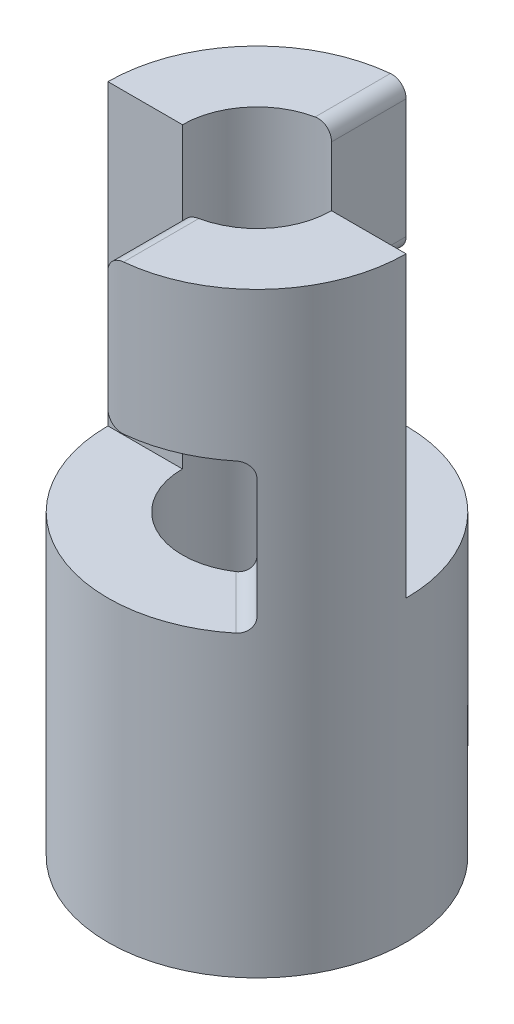
SolidWorks part; units mm, degrees
material "3D Printer ABS - Black"
ref_plane "Front Plane" through (0, 0, 0) normal (0, 0, 1) x (1, 0, 0)
ref_plane "Top Plane" through (0, 0, 0) normal (0, 1, 0) x (1, 0, 0)
ref_plane "Right Plane" through (0, 0, 0) normal (1, 0, 0) x (0, 0, -1)
sketch "Sketch1" plane through (0, 0, 0) normal (0, 1, 0) x (1, 0, 0)
  circle A0 centre (0, 0) radius 6.35
  circle A1 centre (0, 0) radius 3.175
  dimension "D1" = 12.7
extrude "Boss-Extrude1" add sketch "Sketch1" along normal blind 25.4
sketch "Sketch2" plane through (0, 25.4, 0) normal (0, 1, 0) x (1, 0, 0)
  line L0 (0, -3.175) -> (0, -6.35)
  line L1 (0, 3.175) -> (0, 6.35)
  line L2 (-6.35, 0) -> (-3.175, 0)
  line L3 (3.175, 0) -> (6.35, 0)
  circle A0 centre (0, 0) radius 6.35 construction
  circle A1 centre (0, 0) radius 3.175 construction
  circle A2 centre (0, 0) radius 6.35
  circle A3 centre (0, 0) radius 3.175
  circle M4 centre (0, 0) radius 6.35
  circle M5 centre (0, 0) radius 3.175
extrude "Cut-Extrude1" cut sketch "Sketch2" against normal blind 12.7 contours L2 L0 M4 M5 | L3 L1 M5 M4
sketch "Sketch3" plane through (0, 12.7, 0) normal (0, 1, 0) x (1, 0, 0)
  line L0 (4.4901, -4.4901) -> (2.2451, -2.2451)
  line L1 (-2.2451, 2.2451) -> (-4.4901, 4.4901)
  line L2 (0, 3.175) -> (0, 6.35) construction
  line L3 (0, 3.175) -> (0, 6.35)
  line L4 (3.175, 0) -> (6.35, 0) construction
  line L5 (3.175, 0) -> (6.35, 0) construction
  line L6 (0, -3.175) -> (0, -6.35) construction
  line L7 (0, -3.175) -> (0, -6.35)
  arc A0 (0, -6.35) -> (6.35, 0) centre (0, 0) ccw construction
  arc A1 (0, -3.175) -> (3.175, 0) centre (0, 0) ccw construction
  arc A2 (0, 3.175) -> (-3.175, 0) centre (0, 0) ccw construction
  arc A3 (0, 6.35) -> (-6.35, 0) centre (0, 0) ccw construction
  arc A4 (0, 6.35) -> (-4.4901, 4.4901) centre (0, 0) ccw
  arc A5 (0, 3.175) -> (-2.2451, 2.2451) centre (0, 0) ccw
  arc A6 (4.4901, -4.4901) -> (6.35, 0) centre (0, 0) ccw construction
  arc A7 (0, -6.35) -> (4.4901, -4.4901) centre (0, 0) ccw
  arc A8 (-2.2451, 2.2451) -> (-3.175, 0) centre (0, 0) ccw construction
  arc A9 (-4.4901, 4.4901) -> (-6.35, 0) centre (0, 0) ccw construction
  arc A10 (2.2451, -2.2451) -> (3.175, 0) centre (0, 0) ccw construction
  arc A11 (0, -3.175) -> (2.2451, -2.2451) centre (0, 0) ccw
  line M3 (0, -6.35) -> (0, -3.175)
extrude "Cut-Extrude2" [suppressed] cut sketch "Sketch3" along normal blind 6.35 contours A5 L3 A4 L1 | A11 A7 L0 M3
ref_plane "Wrap Plane" through (0, 0, 6.35) normal (0, 0, 1) x (1, 0, 0)
sketch "Sketch5" plane through (0, 0, 6.35) normal (0, 0, 1) x (1, 0, 0)
  line L3 (4.9873, 19.05) -> (0.635, 19.05)
  line L4 (4.9873, 19.05) -> (4.9873, 12.7)
  line L5 (4.9873, 12.7) -> (0, 12.7)
  line L6 (0, 12.7) -> (0, 19.05)
  line L7 (0, 19.05) -> (0, 19.685) construction
  line L8 (0, 12.7) -> (0, 25.4) construction
  line L9 (0.635, 19.05) -> (0, 19.05)
  arc A0 (0, 19.685) -> (0.635, 19.05) centre (0.635, 19.685) ccw construction
  dimension "D1" = 0.635
  dimension "D2" = 4.9873
  dimension "D3" = 6.35
wrap "Wrap6" sketch "Sketch5" wrap type deboss source sketch "Sketch5" thickness 3.175 face at (0, 0, 6.35) parameters "D1"=3.175
pattern_circular "CirPattern1" count 2 over 360 about axis through (0, 19.05, 0) along (0.7071, 0, 0.7071) of "Wrap6"
fillet "Fillet1" radius 0.635 10 edges at (0, 25.4, -4.7625) (0, 25.4, 4.7625) (3.3676, 12.7, 3.3676) (3.3676, 19.05, 3.3676) (0.4755, 19.05, 4.7387) (0, 19.05, 4.7625) (-3.3676, 12.7, -3.3676) (-3.3676, 19.05, -3.3676) (-0.4755, 19.05, -4.7387) (0, 19.05, -4.7625)
split "Split1" bodies to split 106 resulting bodies 107 108
equation "\"D2@Sketch5\"=22.5 / (180) * (2*PI) * 0.25"
